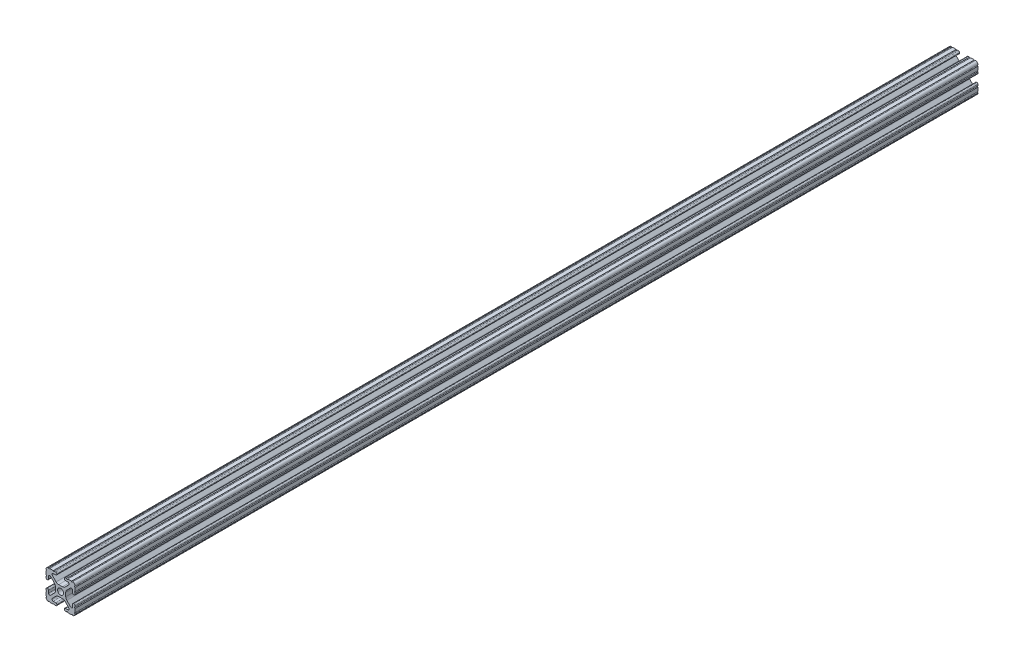
SolidWorks part; units mm, degrees
ref_plane "Front Plane" through (0, 0, 0) normal (0, 0, 1) x (1, 0, 0)
ref_plane "Top Plane" through (0, 0, 0) normal (0, 1, 0) x (1, 0, 0)
ref_plane "Right Plane" through (0, 0, 0) normal (1, 0, 0) x (0, 0, -1)
sketch "Sketch1" plane through (0, 0, 0) normal (0, 0, 1) x (1, 0, 0)
  line L88 (-7.1797, -8.6452) -> (-3.9523, -5.4237)
  line L89 (-1.7093, -4.4958) -> (1.7093, -4.4958)
  line L90 (3.9523, -5.4237) -> (7.1797, -8.6452)
  line L91 (6.4164, -10.4902) -> (4.2875, -10.4902)
  line L92 (3.2385, -11.5392) -> (3.2385, -11.651)
  line L93 (4.2875, -12.7) -> (5.3171, -12.7)
  line L94 (6.3331, -12.7) -> (9.5504, -12.7)
  line L95 (12.7, -9.5504) -> (12.7, -6.3331)
  line L96 (12.7, -5.3171) -> (12.7, -4.2875)
  line L97 (11.651, -3.2385) -> (11.5392, -3.2385)
  line L98 (10.4902, -4.2875) -> (10.4902, -6.4021)
  line L99 (8.7371, -7.1294) -> (5.441, -3.8408)
  line L100 (4.5085, -1.5932) -> (4.5085, 1.5932)
  line L101 (5.441, 3.8408) -> (8.7371, 7.1294)
  line L102 (10.4902, 6.4021) -> (10.4902, 4.2875)
  line L103 (11.5392, 3.2385) -> (11.651, 3.2385)
  line L104 (12.7, 4.2875) -> (12.7, 5.3171)
  line L105 (12.7, 6.3331) -> (12.7, 9.5504)
  line L106 (9.5504, 12.7) -> (6.3331, 12.7)
  line L107 (5.3171, 12.7) -> (4.2875, 12.7)
  line L108 (3.2385, 11.651) -> (3.2385, 11.5392)
  line L109 (4.2875, 10.4902) -> (6.4768, 10.4902)
  line L110 (7.207, 8.7244) -> (3.8983, 5.4232)
  line L111 (1.6558, 4.4958) -> (-1.6558, 4.4958)
  line L112 (-3.8983, 5.4232) -> (-7.207, 8.7244)
  line L113 (-6.4768, 10.4902) -> (-4.2875, 10.4902)
  line L114 (-3.2385, 11.5392) -> (-3.2385, 11.651)
  line L115 (-4.2875, 12.7) -> (-5.3171, 12.7)
  line L116 (-6.3331, 12.7) -> (-9.5504, 12.7)
  line L117 (-12.7, 9.5504) -> (-12.7, 6.3331)
  line L118 (-12.7, 5.3171) -> (-12.7, 4.2875)
  line L119 (-11.651, 3.2385) -> (-11.5392, 3.2385)
  line L120 (-10.4902, 4.2875) -> (-10.4902, 6.4021)
  line L121 (-8.7371, 7.1294) -> (-5.441, 3.8408)
  line L122 (-4.5085, 1.5932) -> (-4.5085, -1.5932)
  line L123 (-5.441, -3.8408) -> (-8.7371, -7.1294)
  line L124 (-10.4902, -6.4021) -> (-10.4902, -4.2875)
  line L125 (-11.5392, -3.2385) -> (-11.651, -3.2385)
  line L126 (-12.7, -4.2875) -> (-12.7, -5.3171)
  line L127 (-12.7, -6.3331) -> (-12.7, -9.5504)
  line L128 (-9.5504, -12.7) -> (-6.3331, -12.7)
  line L129 (-5.3171, -12.7) -> (-4.2875, -12.7)
  line L130 (-3.2385, -11.651) -> (-3.2385, -11.5392)
  line L131 (-4.2875, -10.4902) -> (-6.4164, -10.4902)
  circle A1 centre (0, 0) radius 2.6035
  arc A104 (-7.1797, -8.6452) -> (-6.4164, -10.4902) centre (-6.4164, -9.4098) ccw
  arc A105 (-1.7093, -4.4958) -> (-3.9523, -5.4237) centre (-1.7093, -7.6708) ccw
  arc A106 (3.9523, -5.4237) -> (1.7093, -4.4958) centre (1.7093, -7.6708) ccw
  arc A107 (6.4164, -10.4902) -> (7.1797, -8.6452) centre (6.4164, -9.4098) ccw
  arc A108 (4.2875, -10.4902) -> (3.2385, -11.5392) centre (4.2875, -11.5392) ccw
  arc A109 (3.2385, -11.651) -> (4.2875, -12.7) centre (4.2875, -11.651) ccw
  arc A110 (6.3331, -12.7) -> (5.3171, -12.7) centre (5.8251, -12.7) ccw
  arc A111 (10.5664, -12.6998) -> (9.5504, -12.7) centre (10.0584, -12.7) ccw
  arc A112 (10.5664, -12.6998) -> (12.6998, -10.5664) centre (10.5918, -10.5918) ccw
  arc A113 (12.7, -9.5504) -> (12.6998, -10.5664) centre (12.7, -10.0584) ccw
  arc A114 (12.7, -5.3171) -> (12.7, -6.3331) centre (12.7, -5.8251) ccw
  arc A115 (12.7, -4.2875) -> (11.651, -3.2385) centre (11.651, -4.2875) ccw
  arc A116 (11.5392, -3.2385) -> (10.4902, -4.2875) centre (11.5392, -4.2875) ccw
  arc A117 (8.7371, -7.1294) -> (10.4902, -6.4021) centre (9.4628, -6.4021) ccw
  arc A118 (4.5085, -1.5932) -> (5.441, -3.8408) centre (7.6835, -1.5932) ccw
  arc A119 (5.441, 3.8408) -> (4.5085, 1.5932) centre (7.6835, 1.5932) ccw
  arc A120 (10.4902, 6.4021) -> (8.7371, 7.1294) centre (9.4628, 6.4021) ccw
  arc A121 (10.4902, 4.2875) -> (11.5392, 3.2385) centre (11.5392, 4.2875) ccw
  arc A122 (11.651, 3.2385) -> (12.7, 4.2875) centre (11.651, 4.2875) ccw
  arc A123 (12.7, 6.3331) -> (12.7, 5.3171) centre (12.7, 5.8251) ccw
  arc A124 (12.6998, 10.5664) -> (12.7, 9.5504) centre (12.7, 10.0584) ccw
  arc A125 (12.6998, 10.5664) -> (10.5664, 12.6998) centre (10.5918, 10.5918) ccw
  arc A126 (9.5504, 12.7) -> (10.5664, 12.6998) centre (10.0584, 12.7) ccw
  arc A127 (5.3171, 12.7) -> (6.3331, 12.7) centre (5.8251, 12.7) ccw
  arc A128 (4.2875, 12.7) -> (3.2385, 11.651) centre (4.2875, 11.651) ccw
  arc A129 (3.2385, 11.5392) -> (4.2875, 10.4902) centre (4.2875, 11.5392) ccw
  arc A130 (7.207, 8.7244) -> (6.4768, 10.4902) centre (6.4768, 9.4563) ccw
  arc A131 (1.6558, 4.4958) -> (3.8983, 5.4232) centre (1.6558, 7.6708) ccw
  arc A132 (-3.8983, 5.4232) -> (-1.6558, 4.4958) centre (-1.6558, 7.6708) ccw
  arc A133 (-6.4768, 10.4902) -> (-7.207, 8.7244) centre (-6.4768, 9.4563) ccw
  arc A134 (-4.2875, 10.4902) -> (-3.2385, 11.5392) centre (-4.2875, 11.5392) ccw
  arc A135 (-3.2385, 11.651) -> (-4.2875, 12.7) centre (-4.2875, 11.651) ccw
  arc A136 (-6.3331, 12.7) -> (-5.3171, 12.7) centre (-5.8251, 12.7) ccw
  arc A137 (-10.5664, 12.6998) -> (-9.5504, 12.7) centre (-10.0584, 12.7) ccw
  arc A138 (-10.5664, 12.6998) -> (-12.6998, 10.5664) centre (-10.5918, 10.5918) ccw
  arc A139 (-12.7, 9.5504) -> (-12.6998, 10.5664) centre (-12.7, 10.0584) ccw
  arc A140 (-12.7, 5.3171) -> (-12.7, 6.3331) centre (-12.7, 5.8251) ccw
  arc A141 (-12.7, 4.2875) -> (-11.651, 3.2385) centre (-11.651, 4.2875) ccw
  arc A142 (-11.5392, 3.2385) -> (-10.4902, 4.2875) centre (-11.5392, 4.2875) ccw
  arc A143 (-8.7371, 7.1294) -> (-10.4902, 6.4021) centre (-9.4628, 6.4021) ccw
  arc A144 (-4.5085, 1.5932) -> (-5.441, 3.8408) centre (-7.6835, 1.5932) ccw
  arc A145 (-5.441, -3.8408) -> (-4.5085, -1.5932) centre (-7.6835, -1.5932) ccw
  arc A146 (-10.4902, -6.4021) -> (-8.7371, -7.1294) centre (-9.4628, -6.4021) ccw
  arc A147 (-10.4902, -4.2875) -> (-11.5392, -3.2385) centre (-11.5392, -4.2875) ccw
  arc A148 (-11.651, -3.2385) -> (-12.7, -4.2875) centre (-11.651, -4.2875) ccw
  arc A149 (-12.7, -6.3331) -> (-12.7, -5.3171) centre (-12.7, -5.8251) ccw
  arc A150 (-12.6998, -10.5664) -> (-12.7, -9.5504) centre (-12.7, -10.0584) ccw
  arc A151 (-12.6998, -10.5664) -> (-10.5664, -12.6998) centre (-10.5918, -10.5918) ccw
  arc A152 (-9.5504, -12.7) -> (-10.5664, -12.6998) centre (-10.0584, -12.7) ccw
  arc A153 (-5.3171, -12.7) -> (-6.3331, -12.7) centre (-5.8251, -12.7) ccw
  arc A154 (-4.2875, -12.7) -> (-3.2385, -11.651) centre (-4.2875, -11.651) ccw
  arc A155 (-3.2385, -11.5392) -> (-4.2875, -10.4902) centre (-4.2875, -11.5392) ccw
extrude "Boss-Extrude1" add sketch "Sketch1" along normal mid plane 787.4
sketch "Sketch2" plane through (4.5085, 0, 0) normal (1, 0, 0) x (0, 0, -1)
  line L1 (-393.7, -1.5932) -> (-393.7, 1.5932) construction
  line L2 (0, 0) -> (0, 58.4486) construction
  circle A0 centre (-279.4, 0) radius 3.175
  circle A1 centre (279.4, 0) radius 3.175
  circle A2 centre (-12.7, 0) radius 3.175
  circle A3 centre (12.7, 0) radius 3.175
  dimension "D1" = 6.35
  dimension "D2" = 114.3
  dimension "D3" = 6.35
  dimension "D4" = 266.7
extrude "Cut-Extrude1" cut sketch "Sketch2" against normal through all both and the other way through all
